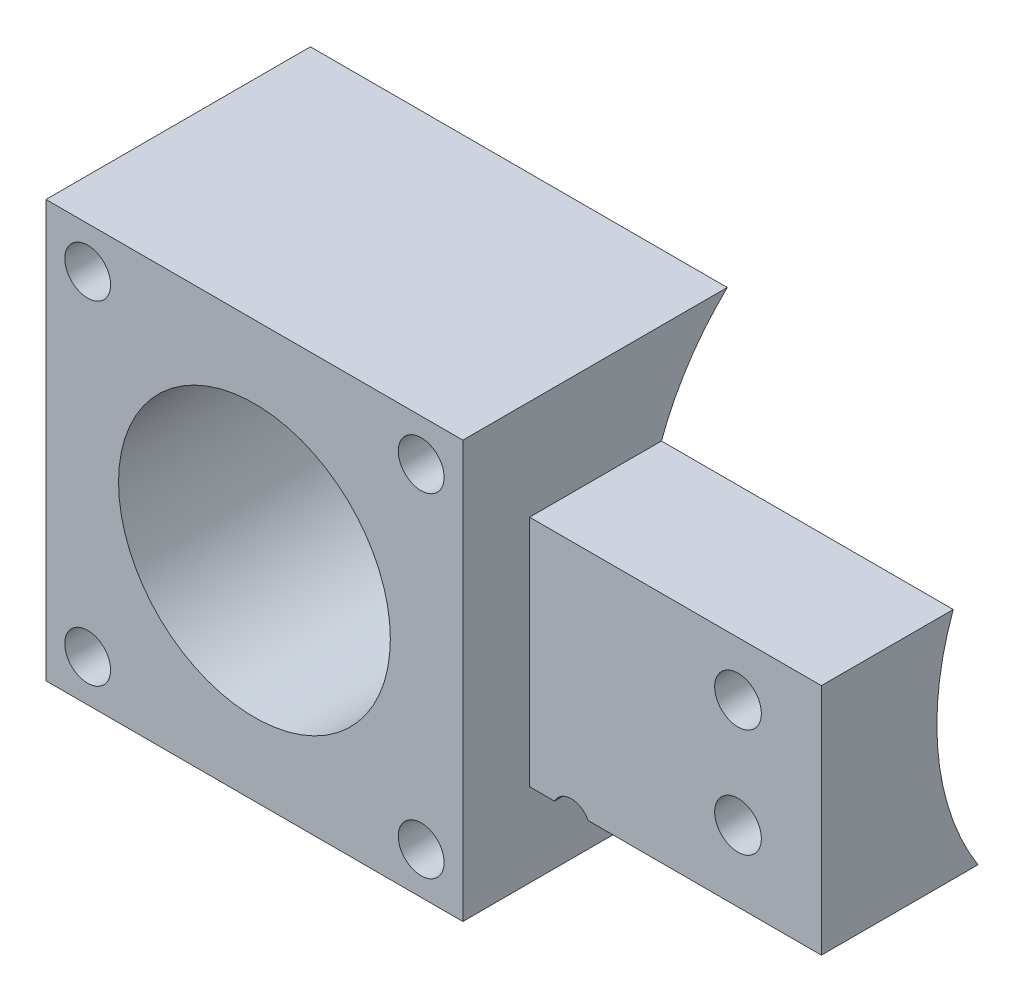
SolidWorks part; units mm, degrees
ref_plane "Front Plane" through (0, 0, 0) normal (0, 0, 1) x (1, 0, 0)
ref_plane "Top Plane" through (0, 0, 0) normal (0, 1, 0) x (1, 0, 0)
ref_plane "Right Plane" through (0, 0, 0) normal (1, 0, 0) x (0, 0, -1)
sketch "Sketch1" plane through (0, 0, 0) normal (0, 0, 1) x (1, 0, 0)
  line L1 (-25, 23) -> (25, 23)
  line L2 (-25, 23) -> (-25, -27)
  line L3 (-25, -27) -> (25, -27)
  line L4 (25, 23) -> (25, -27)
  line L5 (-25, 23) -> (25, -27) construction
  line L6 (-25, -27) -> (25, 23) construction
  circle A0 centre (0, -2) radius 16.3
  circle A1 centre (-20, 18) radius 2.75
  circle A2 centre (20, 18) radius 2.75
  circle A3 centre (20, -22) radius 2.75
  circle A4 centre (-20, -22) radius 2.75
  point P0 (0, -2)
  dimension "D4" = 32.6
  dimension "D6" = 5.5
  dimension "D1" = 2
  dimension "D2" = 50
  dimension "D3" = 50
  dimension "D5" = 20
  dimension "D7" = 20
  dimension "D9" = 20
  dimension "D10" = 20
extrude "Boss-Extrude1" add sketch "Sketch1" along normal blind 53.6
sketch "Sketch2" plane through (0, 0, 0) normal (1, 0, 0) x (0, 0, -1)
  circle A0 centre (0, 0) radius 31.75
  dimension "D1" = 63.5
extrude "Cut-Extrude1" cut sketch "Sketch2" against normal through all and the other way through all
sketch "Sketch3" plane through (-25, 0, 0) normal (-1, 0, 0) x (0, 0, 1)
  line L3 (53.6, 23) -> (21.8875, 23)
  line L4 (16.7052, -27) -> (53.6, -27)
  line L5 (53.6, -27) -> (53.6, 23)
  line L6 (53.6, 23) -> (21.8875, 23)
  line L7 (16.7052, -27) -> (53.6, -27)
  line L8 (53.6, -27) -> (53.6, 23)
  arc A1 (16.7052, -27) -> (21.8875, 23) centre (0, 0) ccw
  arc A2 (16.7052, -27) -> (21.8875, 23) centre (0, 0) ccw
  dimension "D1" = 0
sketch "Sketch4" plane through (25, 0, 0) normal (1, 0, 0) x (0, 0, -1)
  line L3 (-53.6, -27) -> (-16.7052, -27)
  line L4 (-21.8875, 23) -> (-53.6, 23)
  line L5 (-53.6, 23) -> (-53.6, -27)
  line L8 (-53.6, 11) -> (-53.6, -17)
  line L12 (-53.6, 11) -> (-29.7836, 11)
  line L13 (-53.6, 23) -> (-21.8875, 23) construction
  line L14 (0, 0) -> (-85.4701, 0) construction
  line L15 (-53.6, -11) -> (-29.7836, -11) construction
  line L16 (-53.6, -17) -> (-26.8153, -17)
  arc A0 (-21.8875, 23) -> (-16.7052, -27) centre (0, 0) ccw construction
  arc A1 (-21.8875, 23) -> (-16.7052, -27) centre (0, 0) ccw
  arc A2 (-29.7836, 11) -> (-26.8153, -17) centre (0, 0) ccw
  point P0 (-26.5197, -17.4576)
  point P2 (-53.6, -17.6226)
  dimension "D3" = 12
  dimension "D4" = 6
  dimension "D1" = 0
extrude "Boss-Extrude3" add sketch "Sketch4" along normal blind 35
sketch "Sketch12" plane through (0, 0, 53.6) normal (0, 0, 1) x (1, 0, 0)
  line L0 (25, 31) -> (25, -35)
  line L1 (25, -35) -> (85, -35)
  line L2 (85, -35) -> (85, 31)
  line L3 (85, 11) -> (85, -35) construction
  line L4 (85, 31) -> (25, 31) construction
  line L5 (85, 31) -> (25, 31)
extrude "Cut-Extrude7" cut sketch "Sketch12" against normal blind 8
sketch "Sketch9" plane through (0, 0, 0) normal (0, 0, 1) x (1, 0, 0)
  line L0 (30, 22) -> (30, -18) construction
  line L1 (30, -18) -> (70, -18) construction
  line L2 (70, -18) -> (70, 22) construction
  line L3 (70, 22) -> (30, 22) construction
  line L4 (85, 31) -> (25, 31) construction
  line L6 (85, 2) -> (25, 2) construction
  circle A0 centre (30, 22) radius 2.25
  circle A1 centre (70, 22) radius 2.25
  circle A2 centre (70, -18) radius 2.25
  circle A3 centre (30, -18) radius 2.25
  point P0 (30, 22)
  point P2 (70, 22)
  point P4 (70, -18)
  point P6 (30, -18)
  point P25 (70, 2)
  dimension "D4" = 4.5
  dimension "D1" = 60
  dimension "D2" = 5
  dimension "D3" = 40
  dimension "D5" = 29
extrude "Cut-Extrude5" cut sketch "Sketch9" against normal through all both and the other way through all
sketch "Sketch10" plane through (0, 0, 45.6) normal (0, 0, 1) x (1, 0, 0)
  line L0 (50, 4.5) -> (50, -8.5) construction
  line L1 (60, -2) -> (0, -2) construction
  line L3 (30, 22) -> (70, 22) construction
  line L4 (70, 22) -> (50, 22) construction
  line L5 (50, 22) -> (50, -27) construction
  line L6 (-25, -27) -> (25, -27) construction
  line L7 (60, 11) -> (60, -17) construction
  circle A0 centre (50, 4.5) radius 2.8
  circle A1 centre (50, -8.5) radius 2.8
  point P8 (50, -2)
  point P19 (60, -3)
  dimension "D1" = 5.6
  dimension "D2" = 1
  dimension "D3" = 13
extrude "Cut-Extrude6" cut sketch "Sketch10" against normal blind 10 and the other way through all
fillet "Fillet1" radius 8 rebuild error yes
